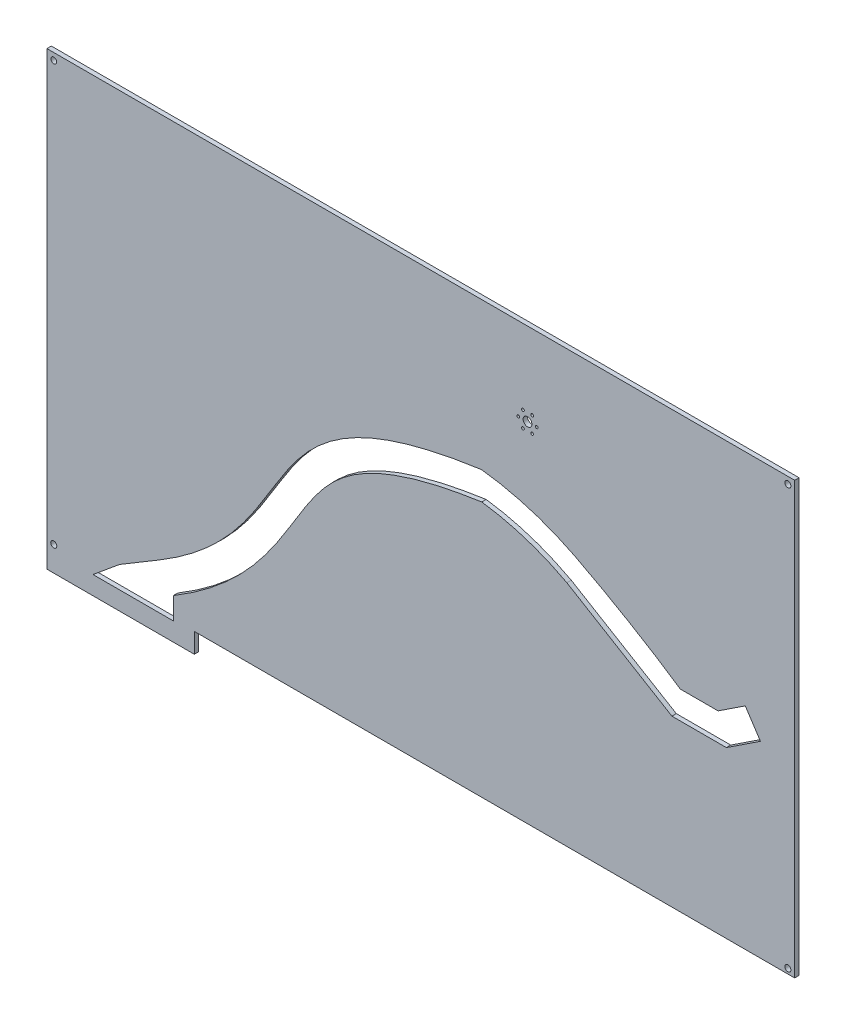
SolidWorks part; units mm, degrees
ref_plane "前视基准面" through (0, 0, 0) normal (0, 0, 1) x (1, 0, 0)
ref_plane "上视基准面" through (0, 0, 0) normal (0, 1, 0) x (1, 0, 0)
ref_plane "右视基准面" through (0, 0, 0) normal (1, 0, 0) x (0, 0, -1)
sketch "Sketch1" plane through (0, 0, 0) normal (0, 0, 1) x (1, 0, 0)
  line L0 (86.3892, 46.5642) -> (136.3892, 46.5642) construction
  line L1 (136.3892, 46.5642) -> (169.6686, 68.4983) construction
  line L2 (-475, -100) -> (-518.0311, -125.7444)
  line L3 (-436.8168, -147.9944) -> (-436.8168, -169.5504)
  line L4 (81.7745, 31.5642) -> (140.8878, 31.5642)
  line L5 (-467.2989, -112.8722) -> (-510.33, -138.6166) construction
  line L6 (140.8878, 31.5642) -> (177.9233, 55.9739)
  line L7 (-459.5978, -125.7444) -> (-459.5978, -149.5504)
  line L8 (-436.8168, -147.9944) -> (215.0808, -147.9944)
  line L9 (215.0808, -147.9944) -> (215.0808, 320)
  line L10 (215.0808, 320) -> (-596.8168, 320)
  line L11 (-596.8168, -150) -> (-596.8168, 320)
  line L12 (215.0808, -147.9944) -> (-596.8168, 320) construction
  line L13 (215.0808, 320) -> (-596.8168, -150) construction
  line L14 (-518.0311, -125.7444) -> (-459.5978, -125.7444) construction
  line L15 (-459.5978, -149.5504) -> (-546.7804, -149.5504)
  line L16 (-546.7804, -149.5504) -> (-518.0311, -125.7444)
  line L17 (90.9712, 61.5642) -> (131.8907, 61.5642)
  line L18 (-436.8168, -169.5504) -> (-596.8168, -169.5504)
  line L19 (-596.8168, -169.5504) -> (-596.8168, -150)
  line L21 (-32.3237, 100) -> (135.1953, 100) construction
  line L22 (-25, 130) -> (125, 130) construction
  line L23 (-28.6108, 115) -> (130.0228, 115) construction
  line L24 (131.8907, 61.5642) -> (161.4139, 81.0227)
  line L25 (177.9233, 55.9739) -> (161.4139, 81.0227)
  line L26 (-21.7014, 128.3139) -> (-25, 130)
  line L27 (-32.3237, 100) -> (81.7745, 31.5642)
  arc A0 (-125, 160) -> (-25, 130) centre (-159.8893, -137.9643) cw
  arc A1 (-28.6108, 115) -> (86.3892, 46.5642) centre (-559.3589, -907.7137) cw construction
  arc A2 (-124.7147, 129.7347) -> (-32.3237, 100) centre (-159.8893, -137.9643) cw
  circle A3 centre (-75, 230) radius 10 construction
  arc A4 (-124.84, 144.8723) -> (-28.6108, 115) centre (-159.8893, -137.9643) cw construction
  arc A5 (-21.7014, 128.3139) -> (90.9712, 61.5642) centre (-559.3589, -907.7137) cw
  circle A6 centre (-589.3757, -142.5578) radius 3.2924
  circle A7 centre (207.6422, -142.5578) radius 3.2924
  circle A8 centre (207.6422, 312.5578) radius 3.2944
  circle A9 centre (-589.3757, 312.5578) radius 3.1635
  arc A10 (135.1953, 100) -> (187.8618, 132.897) centre (303.6181, -111.0302) cw construction
  arc A11 (130.0228, 115) -> (181.4309, 146.4485) centre (303.6181, -111.0302) cw construction
  arc A12 (125, 130) -> (175, 160) centre (303.6181, -111.0302) cw construction
  arc A13 (-35.5202, 101.6861) -> (81.7745, 31.5642) centre (-559.3589, -907.7137) cw construction
  circle A14 centre (-85, 230) radius 1.5
  circle A15 centre (-80, 238.6603) radius 1.5
  circle A16 centre (-70, 238.6603) radius 1.5
  circle A17 centre (-65, 230) radius 1.5
  circle A18 centre (-70, 221.3397) radius 1.5
  circle A19 centre (-80, 221.3397) radius 1.5
  circle A20 centre (-75, 230) radius 4.7625
  spline S0 degree 3 poles (-475, -100) (-419.5406, -66.8201) (-329.5908, 43.116) (-307.6356, 134.2871) (-125, 160) knots 0 0 0 0 0.312224 1 1 1 1
  spline S1 degree 1 poles (-459.5978, -125.7444) (-124.7147, 129.7347) knots 0 0 1 1 construction
  spline S2 degree 3 poles (-459.5978, -125.7444) (-458.1292, -124.8657) (-455.1858, -123.0815) (-449.4714, -119.5247) (-442.5555, -115.0462) (-434.6362, -109.6397) (-424.5564, -102.3861) (-412.8294, -93.2453) (-400.0558, -82.1905) (-388.4865, -71.0922) (-374.5374, -56.3046) (-359.6201, -37.9792) (-344.8908, -16.7676) (-332.3401, 3.2457) (-321.0552, 21.7964) (-310.226, 38.6648) (-299.0796, 53.8348) (-286.8128, 67.5146) (-272.4318, 80.0885) (-257.6527, 89.9241) (-243.4982, 97.442) (-231.5651, 102.8866) (-218.1727, 108.1127) (-203.191, 113.0878) (-189.2817, 116.9961) (-177.2434, 119.9629) (-167.7458, 122.1041) (-157.766, 124.1573) (-149.0369, 125.7919) (-141.7993, 127.0518) (-136.2431, 127.9723) (-131.5022, 128.7191) (-127.6487, 129.3032) (-125.6903, 129.5925) (-124.7147, 129.7347) knots 0 0 0 0 0.007773 0.015545 0.03109 0.046636 0.062181 0.093271 0.124361 0.155452 0.186542 0.248723 0.310904 0.373084 0.435265 0.497446 0.559626 0.621807 0.683988 0.746169 0.777259 0.808349 0.83944 0.87053 0.90162 0.917166 0.932711 0.948256 0.963801 0.971574 0.979346 0.987119 0.991005 0.994892 0.994892 0.994892 0.994892
  spline S3 degree 1 poles (-467.2989, -112.8722) (-124.84, 144.8723) knots 0 0 1 1 construction
  spline S4 degree 3 poles (-467.2989, -112.8722) (-465.8766, -112.0213) (-463.025, -110.2926) (-457.4973, -106.8516) (-450.8174, -102.5249) (-443.1848, -97.3122) (-433.4896, -90.3317) (-422.2436, -81.559) (-410.0336, -70.981) (-398.9994, -60.3828) (-385.707, -46.2708) (-371.4731, -28.7597) (-357.2741, -8.2881) (-344.9599, 11.3612) (-333.6257, 29.9919) (-322.417, 47.4318) (-310.4985, 63.6121) (-297.0179, 78.5777) (-281.0248, 92.4603) (-264.7088, 103.2127) (-249.3105, 111.3089) (-236.4572, 117.1105) (-222.1723, 122.621) (-206.3349, 127.8161) (-191.7467, 131.8615) (-179.1859, 134.915) (-169.3063, 137.1107) (-158.9544, 139.2089) (-149.9221, 140.8739) (-142.4479, 142.1541) (-136.7117, 143.0887) (-130.8627, 143.9946) (-126.8382, 144.5862) (-124.84, 144.8723) knots 0 0 0 0 0.007793 0.015586 0.031173 0.046759 0.062345 0.093518 0.12469 0.155863 0.187036 0.249381 0.311726 0.374071 0.436417 0.498762 0.561107 0.623452 0.685798 0.748143 0.779315 0.810488 0.841661 0.872833 0.904006 0.919592 0.935179 0.950765 0.966351 0.974144 0.981937 0.989731 0.997524 0.997524 0.997524 0.997524 construction
  point P38 (-190, 85.5025)
  point P62 (-75, 230)
  dimension "D5" = 300
  dimension "D8" = 15
  dimension "D14" = 470
  dimension "D18" = 70
  dimension "D22" = 651.8975
  dimension "D24" = 50
  dimension "D26" = 6
  dimension "D27" = 3
  dimension "D28" = 9.525
  dimension "D29" = 20
  dimension "D1" = 105
  dimension "D2" = 100
  dimension "D3" = 350
  dimension "D4" = 260
  dimension "D6" = 100
  dimension "D7" = 30
  dimension "D9" = 15
  dimension "D10" = 115
  dimension "D11" = 50
  dimension "D13" = 15
  dimension "D15" = 190
  dimension "D16" = 320
  dimension "D17" = 20
  dimension "D25" = 811.9
  dimension "D12" = 30
extrude "Boss-Extrude1" add sketch "Sketch1" along normal blind 4.7625
